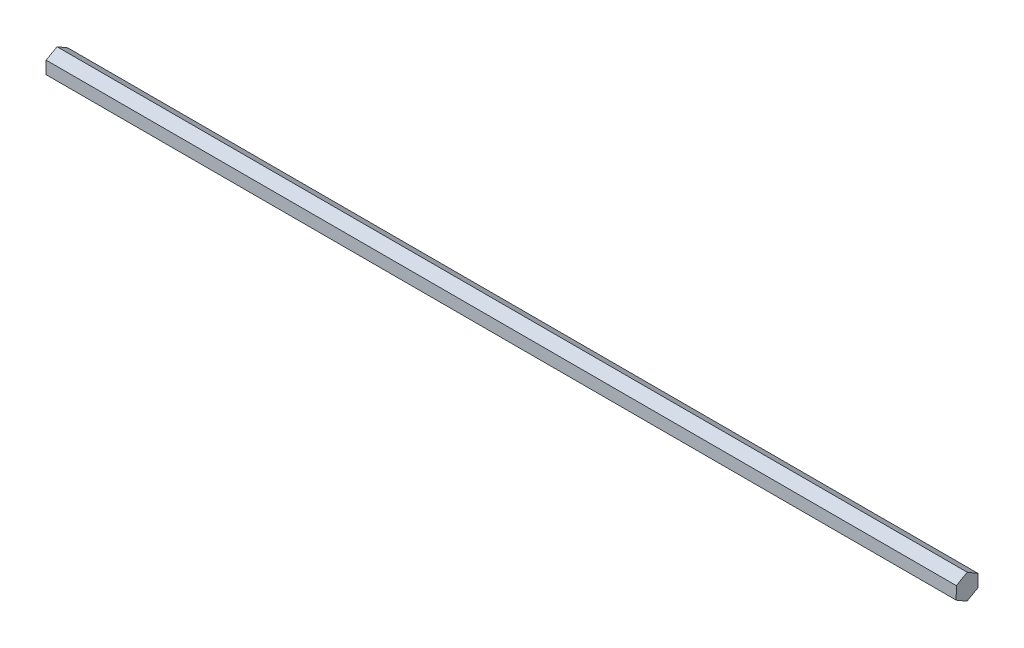
SolidWorks part; units mm, degrees
ref_plane "Front Plane" through (0, 0, 0) normal (0, 0, 1) x (1, 0, 0)
ref_plane "Top Plane" through (0, 0, 0) normal (0, 1, 0) x (1, 0, 0)
ref_plane "Right Plane" through (0, 0, 0) normal (1, 0, 0) x (0, 0, -1)
sketch "Sketch1" plane through (0, 0, 0) normal (1, 0, 0) x (0, 0, -1)
  line L1 (6.3871, 3.6012) -> (0.0748, 7.332)
  line L2 (0.0748, 7.332) -> (-6.3123, 3.7308)
  line L3 (-6.3123, 3.7308) -> (-6.3871, -3.6012)
  line L4 (-6.3871, -3.6012) -> (-0.0748, -7.332)
  line L5 (-0.0748, -7.332) -> (6.3123, -3.7308)
  line L6 (6.3123, -3.7308) -> (6.3871, 3.6012)
  circle A0 centre (0, 0) radius 6.35 construction
  dimension "D1" = 12.7
extrude "Boss-Extrude1" add sketch "Sketch1" along normal blind 533.4
